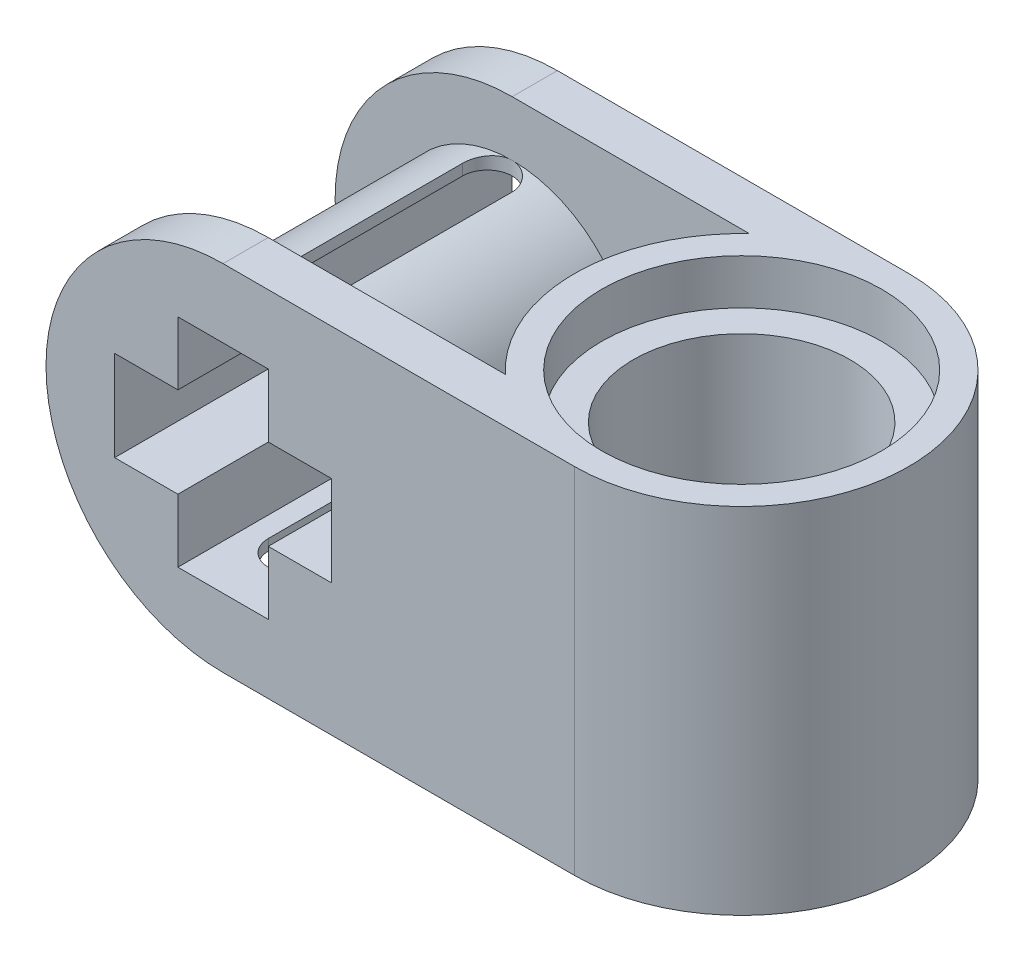
SolidWorks part; units mm, degrees
note: The reader was unsure of these and kept them because the rebuilt part matched: shared geometry of "Sketch1<5>", "Sketch1<6>", "Sketch4<4>", "Sketch4<5>".
ref_plane "Front Plane" through (0, 0, 0) normal (0, 0, 1) x (1, 0, 0)
ref_plane "Top Plane" through (0, 0, 0) normal (0, 1, 0) x (1, 0, 0)
ref_plane "Right Plane" through (0, 0, 0) normal (1, 0, 0) x (0, 0, -1)
sketch "Sketch1" plane through (0, 0, 0) normal (0, 1, 0) x (1, 0, 0)
  line L0 (-11.7, -3.7) -> (-11.7, -2.7)
  line L1 (-11.7, 3.7) -> (-11.7, 2.7)
  line L2 (0, 3.7) -> (-11.7, 3.7)
  line L3 (-11.7, 3.7) -> (-11.7, -3.7)
  line L4 (0, -3.7) -> (-11.7, -3.7)
  line L5 (-11.7, 2.7) -> (-2.5298, 2.7)
  line L6 (-11.7, -2.7) -> (-2.5298, -2.7)
  line L7 (-11.7, 0) -> (-8.2, 0)
  circle A0 centre (0, 0) radius 3.7
  circle A2 centre (0, 0) radius 2.4
  circle A3 centre (0, 0) radius 3.1
  dimension "D1" = 4.8
  dimension "D2" = 6.2
  dimension "D3" = 7.4
extrude "Boss-Extrude2" add sketch "Sketch1" along normal blind 7.84 contours A3 A2 | A0 A3
extrude "Cut-Extrude1" cut sketch "Sketch1<5>" along normal blind 1 contours A3 A2
sketch "Sketch1<5>" plane through (0, 0, 0) normal (0, 1, 0) x (1, 0, 0) same geometry as "Sketch1"
sketch "Sketch3" plane through (0, 7.84, 0) normal (0, 1, 0) x (1, 0, 0)
  circle A0 centre (0, 0) radius 3.1
  circle A1 centre (0, 0) radius 2.4
extrude "Cut-Extrude2" cut sketch "Sketch3" against normal blind 1
extrude "Boss-Extrude3" add sketch "Sketch1<6>" along normal up to surface (7.84 mm away) contours A0 L6 L0 L4 | A0 L2 L1 L5 up to face at (0, 7.84, 3.1)
sketch "Sketch1<6>" plane through (0, 0, 0) normal (0, 1, 0) x (1, 0, 0) same geometry as "Sketch1"
sketch "Sketch4" plane through (0, 0, -3.7) normal (0, 0, -1) x (-1, 0, 0)
  line L0 (7.78, 7.84) -> (11.7, 7.84)
  line L1 (11.7, 7.84) -> (11.7, 0)
  line L2 (11.7, 0) -> (7.78, 0)
  line L3 (8.78, 4.92) -> (8.78, 6.32)
  line L4 (8.78, 1.52) -> (6.78, 1.52)
  line L5 (8.78, 1.52) -> (8.78, 2.92)
  line L6 (8.78, 6.32) -> (6.78, 6.32)
  line L7 (6.78, 1.52) -> (6.78, 2.92)
  line L10 (10.18, 2.92) -> (8.78, 2.92)
  line L11 (10.18, 2.92) -> (10.18, 4.92)
  line L12 (10.18, 4.92) -> (8.78, 4.92)
  line L13 (5.38, 2.92) -> (5.38, 4.92)
  line L17 (6.78, 4.92) -> (5.38, 4.92)
  line L18 (6.78, 4.92) -> (6.78, 6.32)
  line L20 (6.78, 2.92) -> (5.38, 2.92)
  circle A7 centre (7.78, 3.92) radius 2.7
  circle A30 centre (7.78, 3.92) radius 3.92
  line M6 (11.7, 7.84) -> (0, 7.84)
  line M8 (0, 0) -> (11.7, 0)
  line M9 (11.7, 0) -> (11.7, 7.84)
  dimension "D1" = 4.8
  dimension "D2" = 2
  dimension "D4" = 4.8
  dimension "D3" = 2
extrude "Cut-Extrude3" cut sketch "Sketch4" against normal up to surface (7.4 mm away) contours A30 L1 M6 | A30 M8 M9 up to face at (-5.85, 3.92, 3.7)
extrude "Cut-Extrude4" cut sketch "Sketch4<4>" along direction (0, 0, -1) on the side against the normal through all
sketch "Sketch4<4>" plane through (0, 0, -3.7) normal (0, 0, -1) x (-1, 0, 0) same geometry as "Sketch4"
extrude "Boss-Extrude4" add sketch "Sketch4<5>" along direction (0, 0, 1) on the side against the normal through all
sketch "Sketch4<5>" plane through (0, 0, -3.7) normal (0, 0, -1) x (-1, 0, 0) same geometry as "Sketch4"
sketch "Sketch5" plane through (0, 0, 0) normal (0, 1, 0) x (1, 0, 0)
  line L11 (-8.33, -2.15) -> (-8.33, 2.15)
  line L12 (-7.23, -2.15) -> (-7.23, 2.15)
  arc A0 (-7.23, 2.15) -> (-8.33, 2.15) centre (-7.78, 2.15) ccw
  arc A1 (-8.33, -2.15) -> (-7.23, -2.15) centre (-7.78, -2.15) ccw
extrude "Cut-Extrude5" cut sketch "Sketch5" along normal through all
